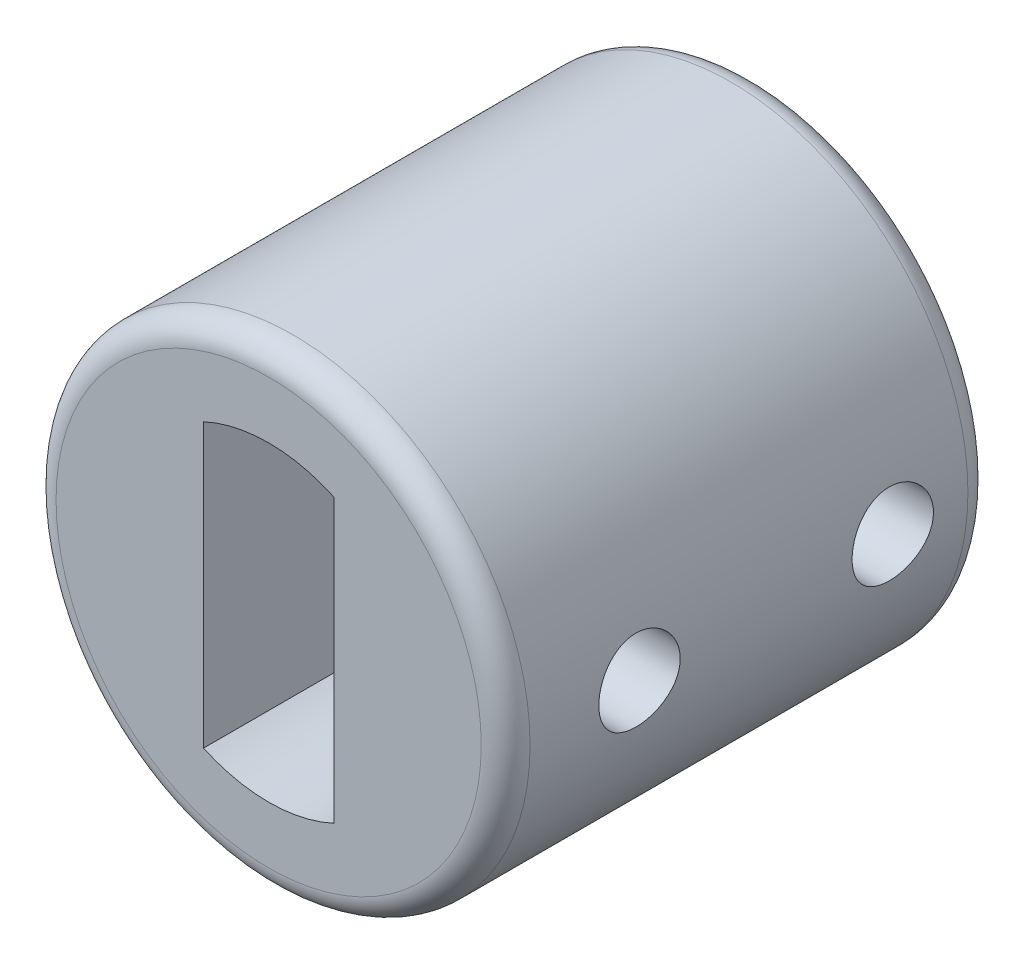
SolidWorks part; units mm, degrees
ref_plane "Front Plane" through (0, 0, 0) normal (0, 0, 1) x (1, 0, 0)
ref_plane "Top Plane" through (0, 0, 0) normal (0, 1, 0) x (1, 0, 0)
ref_plane "Right Plane" through (0, 0, 0) normal (1, 0, 0) x (0, 0, -1)
sketch "Sketch1" plane through (0, 0, 0) normal (0, 0, 1) x (1, 0, 0)
  circle A0 centre (0, 0) radius 7.28
  dimension "D1" = 14.56
extrude "Boss-Extrude1" add sketch "Sketch1" along normal mid plane 14.95
sketch "Sketch3" plane through (0, 0, 7.475) normal (0, 0, 1) x (1, 0, 0)
  line L2 (-2, 4.3415) -> (-2, -4.3415)
  line L4 (2, 4.3415) -> (2, -4.3415)
  line L5 (-2, 4.3415) -> (2, -4.3415) construction
  line L6 (-2, -4.3415) -> (2, 4.3415) construction
  circle A0 centre (0, 0) radius 4.78 construction
  arc A1 (-2, -4.3415) -> (2, -4.3415) centre (0, 0) ccw
  arc A2 (-2, 4.3415) -> (2, 4.3415) centre (0, 0) cw
  dimension "D1" = 9.56
  dimension "D2" = 4
extrude "Cut-Extrude1" cut sketch "Sketch3" against normal blind 8.04 contours L4 A2 L2 A1 region at (0, 0, 7.475)
sketch "Sketch4" plane through (0, 0, -7.475) normal (0, 0, -1) x (-1, 0, 0)
  line L2 (-1.5, 1.9749) -> (-1.5, -1.9749)
  line L4 (1.5, 1.9749) -> (1.5, -1.9749)
  line L5 (-1.5, 1.9749) -> (1.5, -1.9749) construction
  line L6 (-1.5, -1.9749) -> (1.5, 1.9749) construction
  circle A0 centre (0, 0) radius 2.48 construction
  arc A1 (-1.5, 1.9749) -> (1.5, 1.9749) centre (0, 0) cw
  arc A2 (-1.5, -1.9749) -> (1.5, -1.9749) centre (0, 0) ccw
  dimension "D1" = 4.96
  dimension "D2" = 3
extrude "Cut-Extrude2" cut sketch "Sketch4" against normal blind 5 contours L2 A1 L4 A2
chamfer "Chamfer2" distance 0.3 angle 45 2 edges at (-1.5, 0, -2.475) (1.5, 0, -2.475)
chamfer "Chamfer4" distance 0.3 angle 45 4 edges at (0, -2.48, -7.475) (-1.5, 0, -7.475) (0, 2.48, -7.475) (1.5, 0, -7.475)
fillet "Fillet1" radius 0.75 2 edges at (7.28, 0, 7.475) (7.28, 0, -7.475)
ref_axis "Axis1" through (0, 0, 6.725) along (0, 0, -1)
fillet "Fillet2" radius 0.6 2 edges at (0, -4.78, -0.565) (0, 4.78, -0.565)
fillet "Fillet3" radius 0.3 2 edges at (0, 2.48, -2.475) (0, -2.48, -2.475)
ref_plane "Plane1" through (7.28, 0, 0) normal (1, 0, 0) x (0, 0, -1)
ref_plane "Plane2" through (-7.28, 0, 0) normal (-1, 0, 0) x (0, 0, 1)
sketch "Sketch8" plane through (7.28, 0, 0) normal (1, 0, 0) x (0, 0, -1)
  line L0 (-6.725, 0) -> (0, 0) construction
  line L1 (-6.725, 0) -> (6.725, 0) construction
  line L2 (-6.725, -7.28) -> (-6.725, 7.28) construction
  point P0 (-3.3625, 0)
  point P3 (-3.3625, 0)
hole_wizard "M3 Tapped Hole3" positions "Sketch8" profile "Sketch9" tap size "M3" standard "ISO"
cosmetic thread "Hole Thread13" parameters "D1"=5.85, "D2"=3
cosmetic thread "Hole Thread14" parameters "D1"=5.85, "D2"=3
sketch "Sketch9" plane through (7.28, 0, 3.3625) normal (0, 1, 0) x (0, 0, -1)
  line L0 (0, 0) -> (0, 6.7511)
  line L1 (0, 6.7511) -> (1.25, 6)
  line L2 (1.25, 6) -> (1.25, 0)
  line L5 (1.25, 0) -> (0, 0)
  line L10 (0, 6.7511) -> (-1.25, 6) construction
  line L11 (0, -6.35) -> (0, 107.95) construction
  dimension "Tap Drill Dia." = 2.5
  dimension "Tap Drill Depth" = 6
  dimension "Drill Angle" = 118
sketch "Sketch10" plane through (7.28, 0, 0) normal (1, 0, 0) x (0, 0, -1)
  line L0 (2.1087, 0) -> (6.725, 0) construction
  line L1 (-6.725, 0) -> (6.725, 0) construction
  line L2 (6.725, 7.28) -> (6.725, -7.28) construction
  line L3 (0, 8.008) -> (0, -8.008) construction
  point P6 (4.4169, 0)
  dimension "D1" = 2.1087
hole_wizard "M3 Tapped Hole4" positions "Sketch10" profile "Sketch11" tap size "M3" standard "ISO"
sketch "Sketch11" plane through (7.28, 0, -4.4169) normal (0, 1, 0) x (0, 0, -1)
  line L0 (0, 0) -> (0, 7.2511)
  line L1 (0, 7.2511) -> (1.25, 6.5)
  line L2 (1.25, 6.5) -> (1.25, 0)
  line L5 (1.25, 0) -> (0, 0)
  line L10 (0, 7.2511) -> (-1.25, 6.5) construction
  line L11 (0, -6.35) -> (0, 107.95) construction
  dimension "Tap Drill Dia." = 2.5
  dimension "Tap Drill Depth" = 6.5
  dimension "Drill Angle" = 118
cosmetic thread "Hole Thread15" parameters "D1"=6.45, "D2"=3
